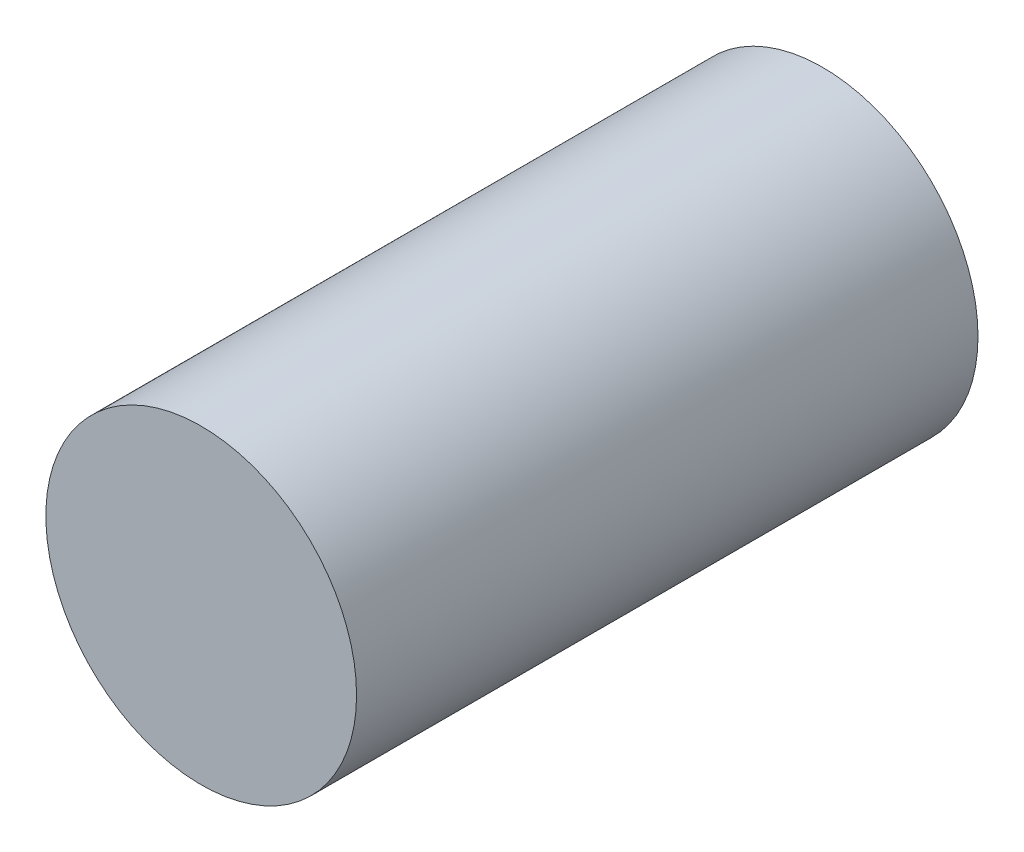
SolidWorks part; units mm, degrees
ref_plane "前视基准面" through (0, 0, 0) normal (0, 0, 1) x (1, 0, 0)
ref_plane "上视基准面" through (0, 0, 0) normal (0, 1, 0) x (1, 0, 0)
ref_plane "右视基准面" through (0, 0, 0) normal (1, 0, 0) x (0, 0, -1)
other "Configuration Table"
sketch "Sketch1" plane through (0, 0, 0) normal (0, 0, 1) x (1, 0, 0)
  circle A0 centre (0, 0) radius 1.5
extrude "Boss-Extrude1" add sketch "Sketch1" along normal blind 6
sketch3d "3DSketch1"
  line L0 (0, 0, 0) -> (0, 0, 6) construction
ref_axis "axis_shank" through (0, 0, 0) along (0, 0, 1)
ref_plane "face_head_bottom" through (0, 0, 6) normal (0, 0, 1) x (1, 0, 0)
